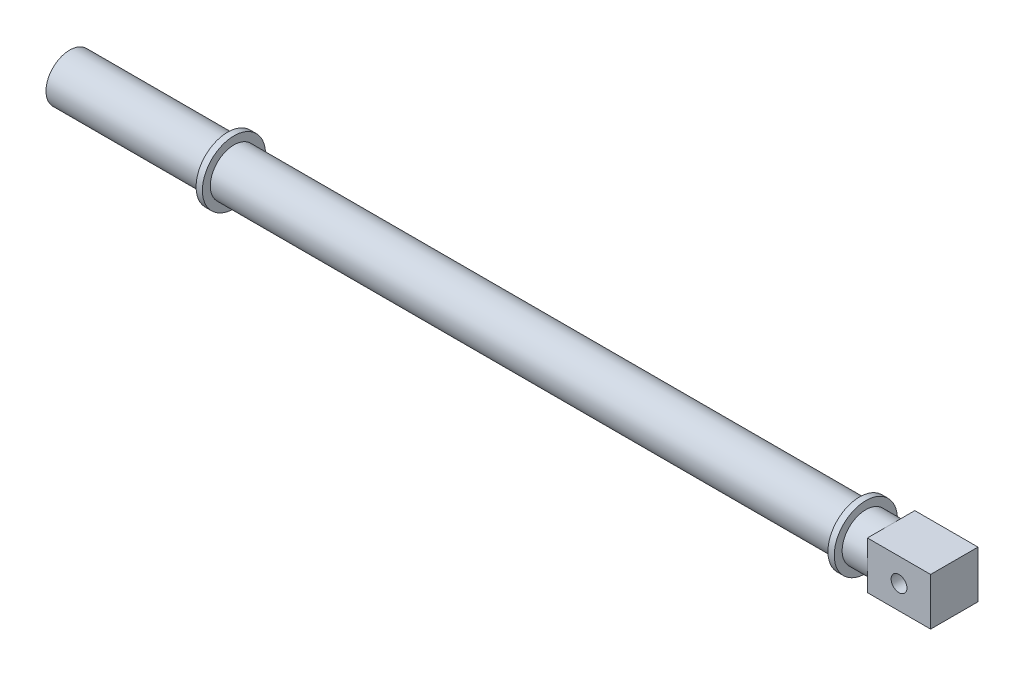
SolidWorks part; units mm, degrees
ref_plane "Plano frontal" through (0, 0, 0) normal (0, 0, 1) x (1, 0, 0)
ref_plane "Plano superior" through (0, 0, 0) normal (0, 1, 0) x (1, 0, 0)
ref_plane "Plano direito" through (0, 0, 0) normal (1, 0, 0) x (0, 0, -1)
sketch "Esboço1" plane through (0, 0, 0) normal (0, 0, 1) x (1, 0, 0)
  line L1 (0, 0) -> (280, 0)
  line L2 (0, 0) -> (0, -7.5)
  line L3 (0, -7.5) -> (280, -7.5)
  line L4 (280, 0) -> (280, -7.5)
revolve "Revolução1" add sketch "Esboço1" angle 360 about L1
sketch "Esboço2" plane through (0, 0, 0) normal (0, 0, 1) x (1, 0, 0)
  circle A0 centre (270, 0) radius 2.5
sketch "Esboço3" plane through (0, 0, 0) normal (0, 0, 1) x (1, 0, 0)
  line L0 (250, 0) -> (252, 0)
  line L1 (252, 0) -> (252, -10)
  line L2 (252, -10) -> (250, -10)
  line L3 (250, -10) -> (250, 0)
  line L4 (50, 0) -> (52, 0)
  line L5 (52, 0) -> (52, -10)
  line L6 (52, -10) -> (50, -10)
  line L7 (50, -10) -> (50, 0)
revolve "Revolução2" add sketch "Esboço3" angle 360 about L4
sketch "Esboço4" plane through (0, 0, 0) normal (0, 0, 1) x (1, 0, 0)
  line L1 (260, 7.5) -> (280, 7.5)
  line L2 (260, 7.5) -> (260, -7.5)
  line L3 (260, -7.5) -> (280, -7.5)
  line L4 (280, 7.5) -> (280, -7.5)
  line L5 (260, 7.5) -> (280, -7.5) construction
  line L6 (260, -7.5) -> (280, 7.5) construction
  point P0 (270, 0)
extrude "Ressalto-extrusão1" add sketch "Esboço4" along normal blind 7.5 and the other way blind 7.5
extrude "Corte-extrusão1" cut sketch "Esboço2" against normal blind 7.5 and the other way blind 7.5
